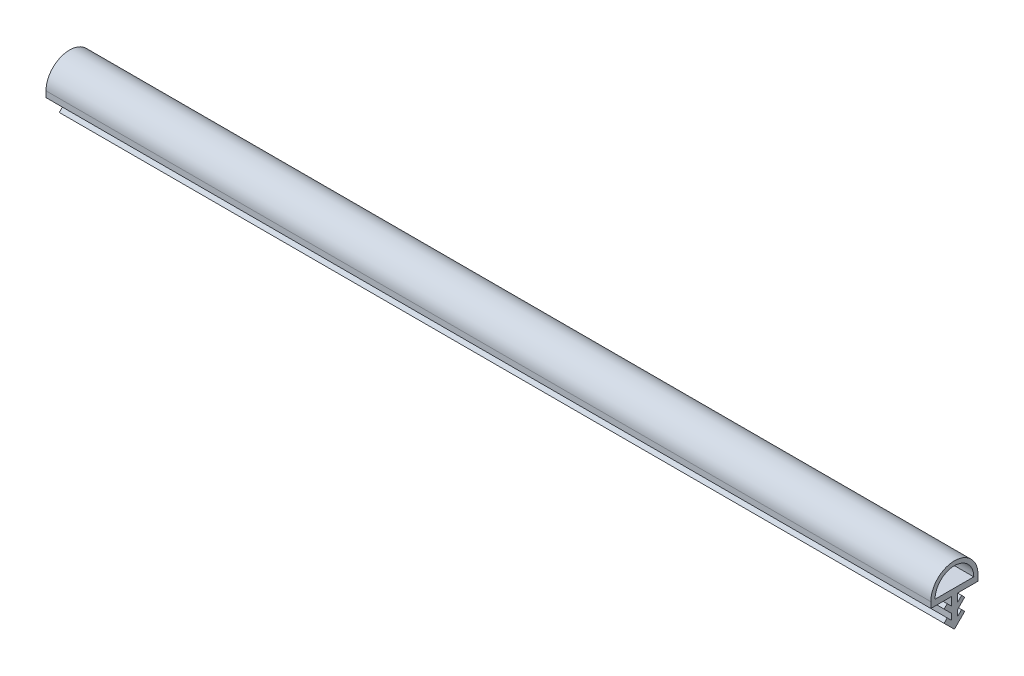
SolidWorks part; units mm, degrees
ref_plane "前视基准面" through (0, 0, 0) normal (0, 0, 1) x (1, 0, 0)
ref_plane "上视基准面" through (0, 0, 0) normal (0, 1, 0) x (1, 0, 0)
ref_plane "右视基准面" through (0, 0, 0) normal (1, 0, 0) x (0, 0, -1)
sketch "草图1" plane through (0, 0, 0) normal (1, 0, 0) x (0, 0, -1)
  line L0 (0, 34.5249) -> (0, -38.0251) construction
  line L1 (-39.9344, 0) -> (41.2072, 0) construction
  line L2 (-4, 0) -> (-0.5, 0)
  line L3 (-0.5, 0) -> (-0.5, -1.4067)
  line L4 (-0.5, -1.4067) -> (-1.2197, -0.6871)
  line L5 (-1.2197, -0.6871) -> (-1.75, -1.2174)
  line L6 (-1.75, -1.2174) -> (-0.5, -2.4674)
  line L7 (-0.5, -2.4674) -> (-0.5, -3.4934)
  line L8 (-0.5, -3.4934) -> (-1.2197, -2.7737)
  line L9 (-1.2197, -2.7737) -> (-1.75, -3.304)
  line L10 (-1.75, -3.304) -> (0, -5.054)
  line L11 (1.75, -3.304) -> (0, -5.054)
  line L12 (1.2197, -2.7737) -> (1.75, -3.304)
  line L13 (0.5, -3.4934) -> (1.2197, -2.7737)
  line L14 (0.5, -2.4674) -> (0.5, -3.4934)
  line L15 (1.75, -1.2174) -> (0.5, -2.4674)
  line L16 (1.2197, -0.6871) -> (1.75, -1.2174)
  line L17 (0.5, -1.4067) -> (1.2197, -0.6871)
  line L18 (0.5, 0) -> (0.5, -1.4067)
  line L19 (4, 0) -> (0.5, 0)
  line L20 (-1.75, -1.2174) -> (-1.75, -7.9663) construction
  line L21 (-4, 0) -> (-4, 1)
  line L22 (4, 0) -> (4, 1)
  line L23 (-5.3438, 5) -> (6.4574, 5) construction
  line L24 (3.282, 1) -> (-3.282, 1)
  arc A0 (4, 1) -> (-4, 1) centre (0, 1) ccw
  arc A1 (3.282, 1) -> (-3.282, 1) centre (0, 1) ccw
  point P29 (-4, 0.5)
  dimension "D1" = 8
  dimension "D2" = 5
  dimension "D3" = 1
  dimension "D4" = 0.75
  dimension "D5" = 0.75
  dimension "D6" = 3.5
extrude "凸台-拉伸1" [suppressed] add sketch "草图1" along normal blind 40 and the other way blind 40
extrude "凸台-拉伸2" add sketch "草图1<2>" along normal blind 75 and the other way blind 75
sketch "草图1<2>" plane through (0, 0, 0) normal (1, 0, 0) x (0, 0, -1) same geometry as "草图1"
